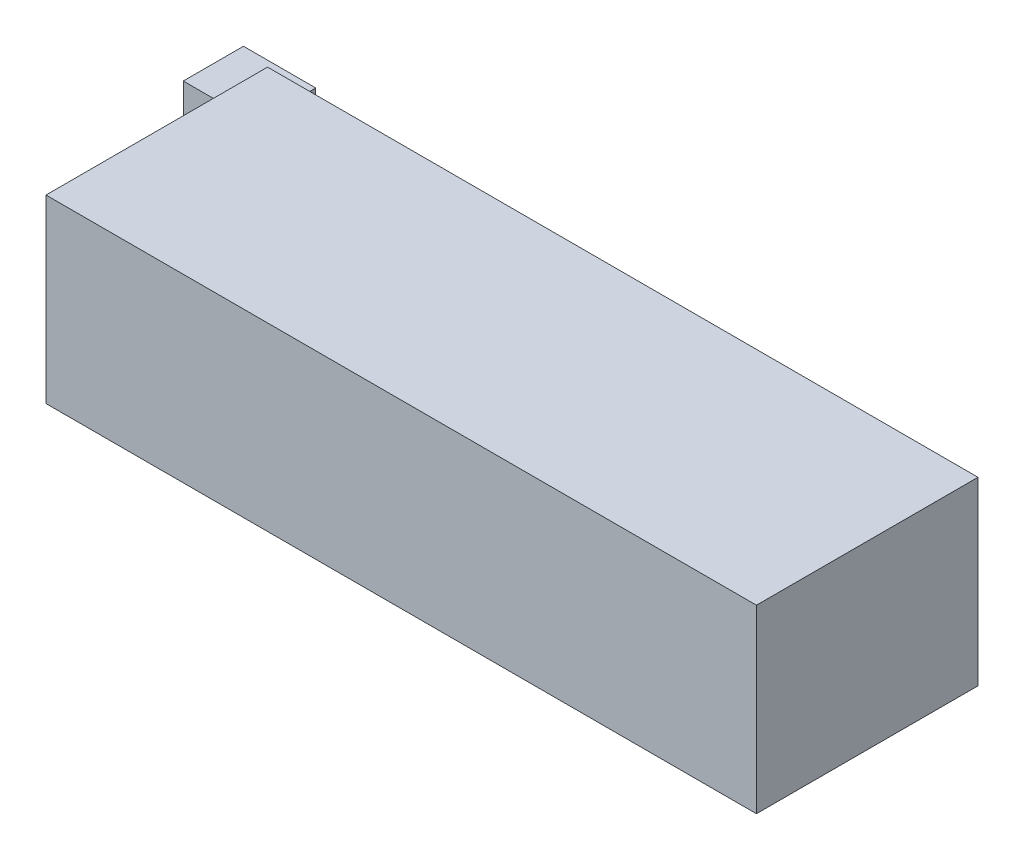
SolidWorks part; units mm, degrees
ref_plane "Front Plane" through (0, 0, 0) normal (0, 0, 1) x (1, 0, 0)
ref_plane "Top Plane" through (0, 0, 0) normal (0, 1, 0) x (1, 0, 0)
ref_plane "Right Plane" through (0, 0, 0) normal (1, 0, 0) x (0, 0, -1)
sketch "Sketch1" plane through (0, 0, 0) normal (0, 1, 0) x (1, 0, 0)
  line L1 (0, 0) -> (74.93, 0)
  line L2 (0, 0) -> (0, -23.368)
  line L3 (0, -23.368) -> (74.93, -23.368)
  line L4 (74.93, 0) -> (74.93, -23.368)
  dimension "D1" = 74.93
  dimension "D2" = 23.368
extrude "Boss-Extrude1" add sketch "Sketch1" along normal blind 19.05
sketch "Sketch2" plane through (0, 0, 0) normal (-1, 0, 0) x (0, 0, 1)
  line L0 (0, 19.05) -> (0, 0) construction
  line L1 (0, 14.605) -> (1.27, 14.605)
  line L2 (0, 14.605) -> (0, 4.445)
  line L3 (0, 4.445) -> (1.27, 4.445)
  line L4 (1.27, 14.605) -> (1.27, 4.445)
  line L5 (3.34, 19.05) -> (3.34, 14.605) construction
  line L6 (0, 19.05) -> (23.368, 19.05) construction
  line L7 (3.34, 4.445) -> (3.34, 0) construction
  line L8 (0, 0) -> (23.368, 0) construction
  line L10 (0, 14.605) -> (-5.08, 14.605)
  line L11 (0, 14.605) -> (0, 4.445)
  line L12 (0, 4.445) -> (-5.08, 4.445)
  line L13 (-5.08, 14.605) -> (-5.08, 4.445)
  line M4 (0, 19.05) -> (0, 0)
  dimension "D1" = 10.16
  dimension "D2" = 5.08
  dimension "D3" = 1.27
extrude "Boss-Extrude2" add sketch "Sketch2" along normal blind 7.62 contours L10 L13 L12 M4 | L4 L1 L3 M4 region at (0, 9.525, 0.635) region at (0, 9.525, -2.54)
fillet "Fillet1" radius 2.54 2 edges at (0, 9.525, 1.27) (0, 9.525, 0)
